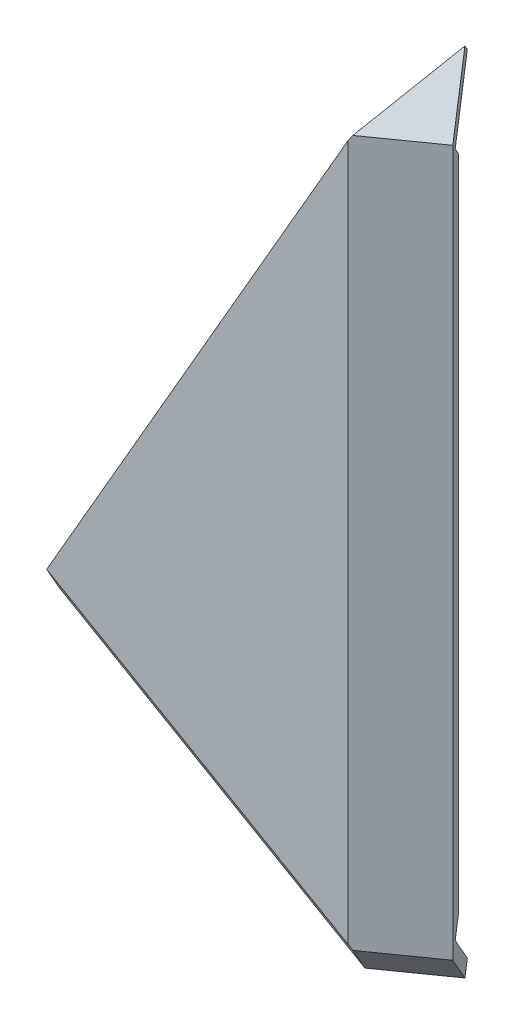
SolidWorks part; units mm, degrees
ref_plane "前基準面" through (0, 0, 0) normal (0, 0, 1) x (1, 0, 0)
ref_plane "上基準面" through (0, 0, 0) normal (0, 1, 0) x (1, 0, 0)
ref_plane "右基準面" through (0, 0, 0) normal (1, 0, 0) x (0, 0, -1)
sketch "草圖1" plane through (0, 0, 0) normal (0, 0, 1) x (1, 0, 0)
  line L0 (161.729, 200.9217) -> (161.729, 10.0028)
  line L1 (161.729, 10.0028) -> (-3.6115, 105.4623)
  line L2 (-3.6115, 105.4623) -> (161.729, 200.9217)
sketch "草圖3" plane through (-31.0463, 53.7737, -43.906) normal (0.4082, -0.7071, 0.5774) x (0.9129, 0.3162, -0.2582)
  line L0 (30.0532, 66.7002) -> (34.5254, 64.4641)
ref_axis "基準軸1" through (159.6878, 197.3861, -2.8868) along (-0.866, -0.5, 0)
ref_axis "基準軸2" through (159.6878, 197.3861, -2.8868) along (0, -1, 0)
ref_plane "平面2" through (0, 0, -2.8868) normal (0, 0, 1) x (1, 0, 0)
sketch "草圖4" plane through (0, 0, -2.8868) normal (0, 0, 1) x (1, 0, 0)
  line L0 (159.6878, 197.3861) -> (159.6878, 13.5384)
  line L1 (159.6878, 13.5384) -> (0.471, 105.4623)
  line L2 (0.471, 105.4623) -> (159.6878, 197.3861)
loft "疊層拉伸1" add profiles "草圖1", "草圖4" connector at (-3.6115, 105.4623, 0) connector at (0.471, 105.4623, -2.8868)
ref_plane "平面3" through (-15.5231, 26.8868, 43.906) normal (-0.2887, 0.5, 0.8165) x (0.9574, 0.1508, 0.2462)
sketch "草圖5" plane through (-15.5231, 26.8868, 43.906) normal (-0.2887, 0.5, 0.8165) x (0.9574, 0.1508, 0.2462)
  line L0 (12.4413, 89.9385) -> (3.9132, 108.0292)
  line L1 (12.4413, 89.9385) -> (-13.1428, 144.2106) construction
  line L2 (3.9132, 108.0292) -> (176.6058, 189.4373)
  line L3 (159.5498, 225.6186) -> (185.1338, 171.3466) construction
  line L4 (176.6058, 189.4373) -> (185.1338, 171.3466)
  line L5 (185.1338, 171.3466) -> (12.4413, 89.9385)
  point P10 (8.1772, 98.9839)
  dimension "D1" = 10
ref_plane "平面4" through (-14.5025, 25.1191, 41.0193) normal (-0.2887, 0.5, 0.8165) x (0.9574, 0.1508, 0.2462)
sketch "草圖6" plane through (-14.5025, 25.1191, 41.0193) normal (-0.2887, 0.5, 0.8165) x (0.9574, 0.1508, 0.2462)
  line L0 (15.6393, 91.4461) -> (7.1112, 109.5368)
  line L1 (15.6393, 91.4461) -> (-9.9448, 145.7181) construction
  line L2 (7.1112, 109.5368) -> (173.4078, 187.9297)
  line L3 (156.3517, 224.1111) -> (181.9358, 169.839) construction
  line L4 (173.4078, 187.9297) -> (181.9358, 169.839)
  line L5 (181.9358, 169.839) -> (15.6393, 91.4461)
  dimension "D1" = 20
loft "疊層拉伸2" add profiles "草圖5", "草圖6" connector at (153.5641, 215.0638, -11.547) connector at (151.5228, 211.5283, -14.4338)
sketch "草圖7" plane through (107.8194, 0, -76.2398) normal (0.8165, 0, -0.5774) x (-0.5774, 0, -0.8165)
  line L0 (-93.3743, 200.9217) -> (-89.8388, 197.3861)
  line L1 (-89.8388, 197.3861) -> (-89.8388, 13.5384)
  line L2 (-89.8388, 13.5384) -> (-93.3743, 10.0028)
  line L3 (-93.3743, 10.0028) -> (-93.3743, 200.9217)
extrude "填料-伸長1" add sketch "草圖7" along normal blind 20
sketch "草圖8" plane through (29.8424, 51.6886, 42.2035) normal (-0.4082, -0.7071, -0.5774) x (0.9129, -0.3162, -0.2582)
  line L0 (-32.1748, -68.9363) -> (-36.647, -66.7002)
  line L1 (-36.647, -66.7002) -> (-32.1748, -68.9363) construction
  line L2 (-36.647, -66.7002) -> (84.1007, -127.074) construction
  line L3 (-36.647, -66.7002) -> (144.4746, -6.3264)
  line L4 (144.4746, -6.3264) -> (142.2385, -10.7985)
  line L5 (142.2385, -10.7985) -> (-32.1748, -68.9363)
extrude "填料-伸長2" add sketch "草圖8" along normal blind 20
other "移動面1" face at (173.9765, 81.5974, -8.6603) face at (52.2675, 59.0584, -8.6603) face at (106.6155, 105.4623, 0) face at (116.3114, 184.1279, -5.7735) offset 3 parameters "D1"=3
ref_plane "平面5" through (-5.8718, 0, 4.152) normal (-0.8165, 0, 0.5774) x (0.5774, 0, 0.8165)
sketch "草圖10" plane through (-5.8718, 0, 4.152) normal (-0.8165, 0, 0.5774) x (0.5774, 0, 0.8165)
  line L0 (-2.0851, 105.4623) -> (-16.2273, 91.3201)
  line L1 (-16.2273, 91.3201) -> (-30.3694, 105.4623)
  line L2 (-30.3694, 105.4623) -> (75.6966, 211.5283) construction
  line L3 (-30.3694, 105.4623) -> (75.6966, -0.6038) construction
  line L4 (-30.3694, 105.4623) -> (-16.2273, 119.6044)
  line L5 (-16.2273, 119.6044) -> (-2.0851, 105.4623)
extrude "填料-伸長4" add sketch "草圖10" against normal blind 4
ref_plane "平面6" through (25.7993, -44.6857, 36.4857) normal (0.4082, -0.7071, 0.5774) x (-0.9129, -0.3162, 0.2582)
sketch "草圖11" plane through (25.7993, -44.6857, 36.4857) normal (0.4082, -0.7071, 0.5774) x (-0.9129, -0.3162, 0.2582)
  line L0 (-150.8009, -6.3264) -> (-141.8566, 11.5622)
  line L1 (-141.8566, 11.5622) -> (-159.7452, 20.5065)
  line L2 (-159.7452, 20.5065) -> (-168.6895, 2.6179)
  line L3 (-168.6895, 2.6179) -> (-150.8009, -6.3264)
extrude "填料-伸長5" add sketch "草圖11" against normal blind 4
ref_plane "平面7" through (86.688, 150.148, 122.5953) normal (0.4082, 0.7071, 0.5774) x (0.9129, -0.3162, -0.2582)
sketch "草圖12" plane through (86.688, 150.148, 122.5953) normal (0.4082, 0.7071, 0.5774) x (0.9129, -0.3162, -0.2582)
  line L0 (84.1007, 127.074) -> (101.9893, 136.0183)
  line L1 (101.9893, 136.0183) -> (93.045, 153.9068)
  line L2 (93.045, 153.9068) -> (-41.1191, 86.8248) construction
  line L3 (93.045, 153.9068) -> (160.127, 19.7428) construction
  line L4 (93.045, 153.9068) -> (75.1564, 144.9626)
  line L5 (84.1007, 127.074) -> (75.1564, 144.9626) construction
  line L6 (75.1564, 144.9626) -> (84.1007, 127.074)
extrude "填料-伸長6" add sketch "草圖12" against normal blind 4
sketch "草圖13" plane through (0, 0, 3) normal (0, 0, 1) x (1, 0, 0)
  line L0 (171.626, 218.0638) -> (70.0278, 42.0904)
  line L1 (155.2961, -7.1393) -> (-15.2406, 91.3201) construction
  line L2 (70.0278, 42.0904) -> (179.2637, -20.977)
  line L3 (179.2637, -20.977) -> (300.5273, 191.6801)
  line L4 (300.5273, 191.6801) -> (171.626, 218.0638)
extrude "除料-伸長1" [suppressed] cut sketch "草圖13" against normal blind 52
sketch "草圖14" plane through (0, 0, 3) normal (0, 0, 1) x (1, 0, 0)
  line L0 (171.626, 218.0638) -> (70.0278, 42.0904)
  line L1 (155.2961, -7.1393) -> (-15.2406, 91.3201) construction
  line L2 (70.0278, 42.0904) -> (-62.3325, 118.5087)
  line L3 (-62.3325, 118.5087) -> (56.076, 323.5983)
  line L4 (56.076, 323.5983) -> (171.626, 218.0638)
extrude "除料-伸長2" cut sketch "草圖14" against normal blind 52
